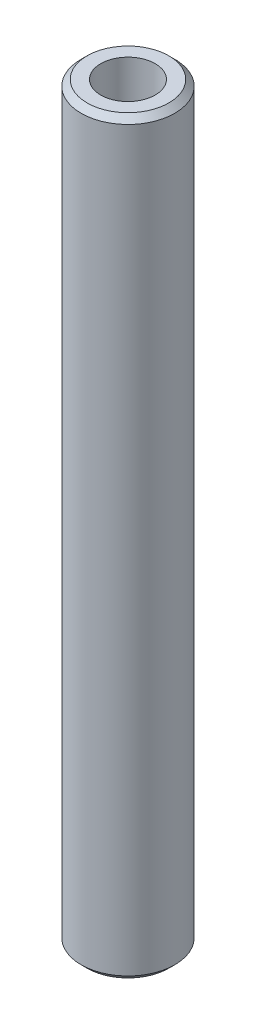
SolidWorks part; units mm, degrees
ref_plane "Front Plane" through (0, 0, 0) normal (0, 0, 1) x (1, 0, 0)
ref_plane "Top Plane" through (0, 0, 0) normal (0, 1, 0) x (1, 0, 0)
ref_plane "Right Plane" through (0, 0, 0) normal (1, 0, 0) x (0, 0, -1)
sketch "Sketch1" plane through (0, 0, 0) normal (0, 1, 0) x (1, 0, 0)
  circle A0 centre (0, 0) radius 37.5
  dimension "SHAFT_OD" = 75
extrude "Boss-Extrude1" add sketch "Sketch1" along normal blind 600
sketch "Sketch2" plane through (0, 0, 0) normal (0, 1, 0) x (1, 0, 0)
  circle A0 centre (0, 0) radius 21.8061
  dimension "BORE_D" = 43.6123
extrude "Cut-Extrude1" cut sketch "Sketch2" along normal through all
chamfer "Chamfer1" distance 4.7871 angle 45 2 edges at (0, 600, 37.5) (0, 0, 37.5)
